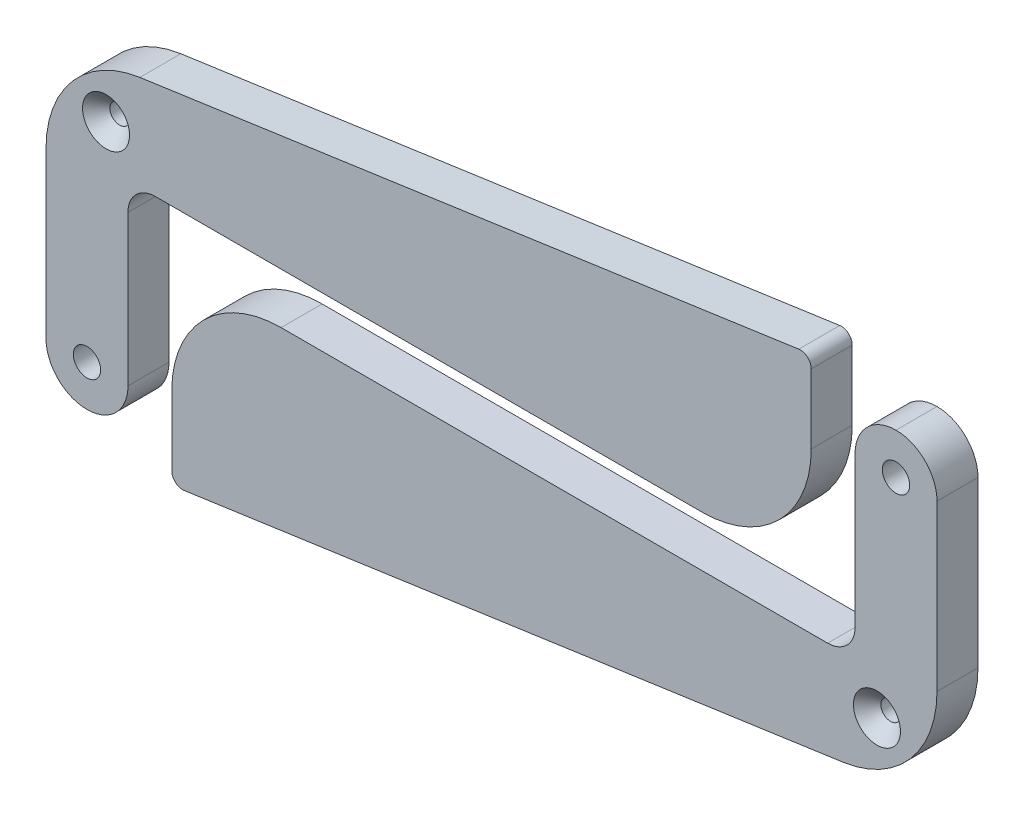
SolidWorks part; units mm, degrees
ref_plane "Front Plane" through (0, 0, 0) normal (0, 0, 1) x (1, 0, 0)
ref_plane "Top Plane" through (0, 0, 0) normal (0, 1, 0) x (1, 0, 0)
ref_plane "Right Plane" through (0, 0, 0) normal (1, 0, 0) x (0, 0, -1)
sketch "Sketch1" plane through (0, 0, 0) normal (0, 0, 1) x (1, 0, 0)
  line L1 (0, 0) -> (177.8, 0)
  line L2 (0, 0) -> (0, 19.05)
  line L4 (177.8, 0) -> (177.8, 44.45)
  line L6 (177.8, 44.45) -> (0, 19.05)
  point P5 (0, 22.8908)
  dimension "D1" = 19.05
  dimension "D2" = 25.4
  dimension "D4" = 177.8
extrude "Boss-Extrude1" add sketch "Sketch1" along normal blind 9.525
sketch "Sketch4" plane through (0, 0, 9.525) normal (0, 0, 1) x (1, 0, 0)
  line L0 (0, 19.05) -> (0, 0) construction
  line L1 (0, 0) -> (19.05, 0)
  line L2 (0, 0) -> (0, -50.8)
  line L3 (0, -50.8) -> (19.05, -50.8)
  line L4 (19.05, 0) -> (19.05, -50.8)
  dimension "D1" = 50.8
extrude "Boss-Extrude2" add sketch "Sketch4" against normal up to surface (9.525 mm away) contours L2 L3 L4 L1 up to face at (88.9, 15.875, 0)
fillet "Fillet1" radius 2.54 1 edges at (177.8, 44.45, 4.7625)
sketch "Sketch2" plane through (0, 0, 9.525) normal (0, 0, 1) x (1, 0, 0)
  line L0 (0, -41.275) -> (9.525, -41.275) construction
  line L2 (9.525, -41.275) -> (19.05, -41.275) construction
  line L3 (19.05, 0) -> (19.05, -50.8) construction
  line L4 (9.525, -41.275) -> (9.525, -50.8) construction
  line L5 (0, -50.8) -> (19.05, -50.8) construction
  circle A0 centre (9.525, -41.275) radius 3.175
  point P2 (0, 0)
extrude "Cut-Extrude1" cut sketch "Sketch2" against normal through all
fillet "Fillet2" radius 25.4 1 edges at (177.8, 0, 4.7625)
fillet "Fillet3" radius 25.4 1 edges at (0, 19.05, 4.7625)
fillet "Fillet4" radius 6.35 1 edges at (19.05, 0, 4.7625)
fillet "Fillet5" radius 9.525 2 edges at (19.05, -50.8, 4.7625) (0, -50.8, 4.7625)
sketch "Sketch6" plane through (0, 0, 9.525) normal (0, 0, 1) x (1, 0, 0)
  line L0 (9.525, -41.275) -> (13.9525, 9.3317) construction
  line L1 (19.05, -6.35) -> (19.05, -41.275) construction
  circle A0 centre (13.9525, 9.3317) radius 2.286
  dimension "D3" = 4.572
  dimension "D1" = 5
  dimension "D2" = 50.8
extrude "Cut-Extrude3" cut sketch "Sketch6" against normal through all
chamfer "Chamfer1" distance 3.175 angle 45 1 edges at (16.2385, 9.3317, 9.525)
sketch "Sketch8" plane through (0, 0, 9.525) normal (0, 0, 1) x (1, 0, 0)
  point P0 (103.5103, -5.8843)
  point P1 (0, 0)
  point P2 (0, 0)
  point P3 (102.3963, -6.3813)
  point P4 (77.4875, -26.7547)
  point P5 (0, 0)
  point P6 (84.2454, -28.1193)
  point P7 (0, 0)
  point P8 (114.7424, -14.0367)
  point P9 (0, 0)
  point P10 (95.0869, -7.0113)
  point P11 (0, 0)
  point P12 (104.5196, -5.5944)
  point P13 (0, 0)
  point P14 (98.7159, -6.0336)
  point P15 (0, 0)
  point P16 (103.5103, -5.8843)
ref_axis "Axis1" through (103.5103, -5.8843, 9.525) along (0, 0, 1)
pattern_circular "CirPattern1" count 2 over 360 about axis through (103.5103, -5.8843, 9.525) along (0, 0, 1) of bodies 106
